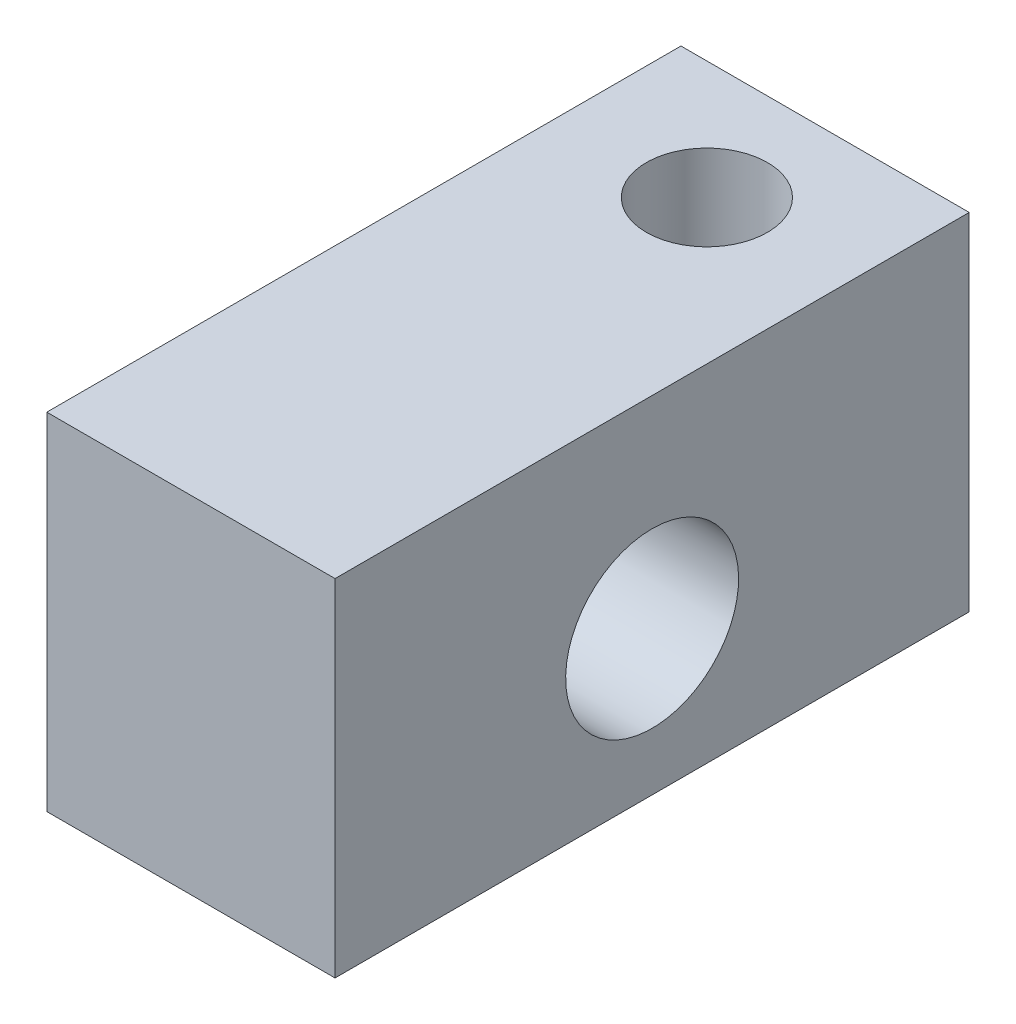
SolidWorks part; units mm, degrees
ref_plane "Front Plane" through (0, 0, 0) normal (0, 0, 1) x (1, 0, 0)
ref_plane "Top Plane" through (0, 0, 0) normal (0, 1, 0) x (1, 0, 0)
ref_plane "Right Plane" through (0, 0, 0) normal (1, 0, 0) x (0, 0, -1)
sketch "Sketch1" plane through (0, 0, 0) normal (0, 0, 1) x (1, 0, 0)
  line L1 (0, 0) -> (5, 0)
  line L2 (0, 0) -> (0, -6)
  line L3 (0, -6) -> (5, -6)
  line L4 (5, 0) -> (5, -6)
  dimension "D1" = 5
  dimension "D2" = 6
extrude "Boss-Extrude1" add sketch "Sketch1" along normal blind 11
sketch "Sketch2" plane through (5, 0, 0) normal (1, 0, 0) x (0, 0, -1)
  line L0 (-11, -6) -> (0, -6) construction
  line L1 (-5.5, -3.5) -> (-5.5, -6) construction
  circle A0 centre (-5.5, -3.5) radius 1.5
  dimension "D1" = 3
  dimension "D2" = 2.5
extrude "Cut-Extrude1" cut sketch "Sketch2" against normal up to next
sketch "Sketch3" plane through (0, 0, 0) normal (0, 1, 0) x (1, 0, 0)
  line L0 (5, -11) -> (5, 0) construction
  line L1 (5, 0) -> (0, 0) construction
  circle A0 centre (2.5, -2.05) radius 1.05
  dimension "D1" = 2.5
  dimension "D3" = 2.1
  dimension "D2" = 2.05
extrude "Cut-Extrude2" cut sketch "Sketch3" against normal blind 4
sketch "Sketch4" plane through (0, -6, 0) normal (0, -1, 0) x (1, 0, 0)
  line L0 (2.5, 10) -> (2.5, 11) construction
  line L1 (0, 11) -> (5, 11) construction
  circle A0 centre (2.5, 8.95) radius 1.05
  dimension "D2" = 2.1
  dimension "D1" = 1
extrude "Cut-Extrude3" cut sketch "Sketch4" against normal blind 4
